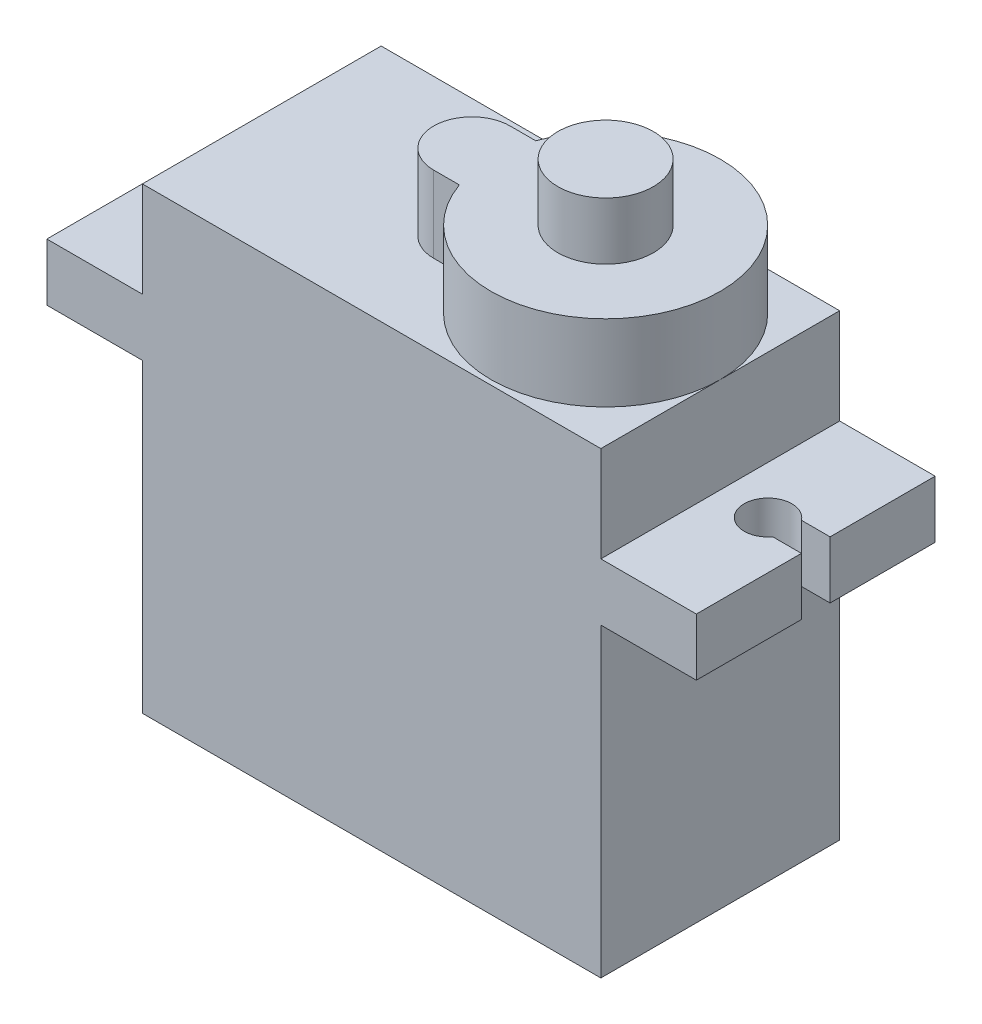
SolidWorks part; units mm, degrees
material "1060 Alloy"
ref_plane "Front Plane" through (0, 0, 0) normal (0, 0, 1) x (1, 0, 0)
ref_plane "Top Plane" through (0, 0, 0) normal (0, 1, 0) x (1, 0, 0)
ref_plane "Right Plane" through (0, 0, 0) normal (1, 0, 0) x (0, 0, -1)
sketch "Sketch1" plane through (0, 0, 0) normal (0, 1, 0) x (1, 0, 0)
  line L1 (-12, -6.25) -> (12, -6.25)
  line L2 (-12, -6.25) -> (-12, 6.25)
  line L3 (-12, 6.25) -> (12, 6.25)
  line L4 (12, -6.25) -> (12, 6.25)
  line L5 (-12, -6.25) -> (12, 6.25) construction
  line L6 (-12, 6.25) -> (12, -6.25) construction
  point P0 (0, 0)
  dimension "D1" = 12.5
  dimension "D2" = 24
extrude "Boss-Extrude1" add sketch "Sketch1" along normal blind 24
sketch "Sketch2" plane through (12, 0, 0) normal (1, 0, 0) x (0, 0, -1)
  line L0 (-6.25, 24) -> (-6.25, 0) construction
  line L1 (-6.25, 19) -> (6.25, 19)
  line L2 (-6.25, 19) -> (-6.25, 16)
  line L3 (-6.25, 16) -> (6.25, 16)
  line L4 (6.25, 19) -> (6.25, 16)
  line L5 (6.25, 24) -> (6.25, 0) construction
  line L7 (-6.25, 0) -> (6.25, 0) construction
  dimension "D1" = 16
  dimension "D2" = 3
extrude "Boss-Extrude2" add sketch "Sketch2" along normal blind 5 and the other way blind 29
sketch "Sketch3" plane through (0, 24, 0) normal (0, 1, 0) x (1, 0, 0)
  line L3 (-1, 2) -> (0.3431, 2)
  line L4 (-1, -2) -> (0.3431, -2)
  line L5 (-12, 6.25) -> (-12, -6.25) construction
  line L6 (12, -6.25) -> (12, 6.25) construction
  circle A0 centre (6, 0) radius 2.5
  arc A1 (0.3431, -2) -> (0.3431, 2) centre (6, 0) ccw
  arc A2 (-1, 2) -> (-1, -2) centre (-1, 0) ccw
  dimension "D1" = 5
  dimension "D3" = 2
  dimension "D5" = 12
  dimension "D2" = 11
  dimension "D4" = 6
extrude "Boss-Extrude3" add sketch "Sketch3" along normal blind 4
sketch "Sketch4" plane through (0, 28, 0) normal (0, 1, 0) x (1, 0, 0)
  circle A0 centre (6, 0) radius 2.5
extrude "Boss-Extrude4" add sketch "Sketch4" along normal blind 3 and the other way up to surface (4 mm away) other way up to face at (2.2372, 24, 0)
sketch "Sketch5" plane through (0, 19, 0) normal (0, 1, 0) x (1, 0, 0)
  line L0 (-17, -0.75) -> (-15.5, -0.75)
  line L1 (-17, 6.25) -> (-17, -6.25) construction
  line L3 (-15.5, 0.75) -> (-17, 0.75)
  line L4 (-17, 0.75) -> (-17, -0.75)
  arc A0 (-15.5, -0.75) -> (-15.5, 0.75) centre (-14.5, 0) ccw
  point P1 (-17, 0)
  dimension "D1" = 2.5
  dimension "D2" = 1.5
  dimension "D3" = 2.5
extrude "Cut-Extrude1" cut sketch "Sketch5" against normal blind 4
mirror "Mirror1" about plane through (0, 0, 0) normal (1, 0, 0) of "Cut-Extrude1"
equation "\"D2@Sketch3\"=9+\"D3@Sketch3\""
